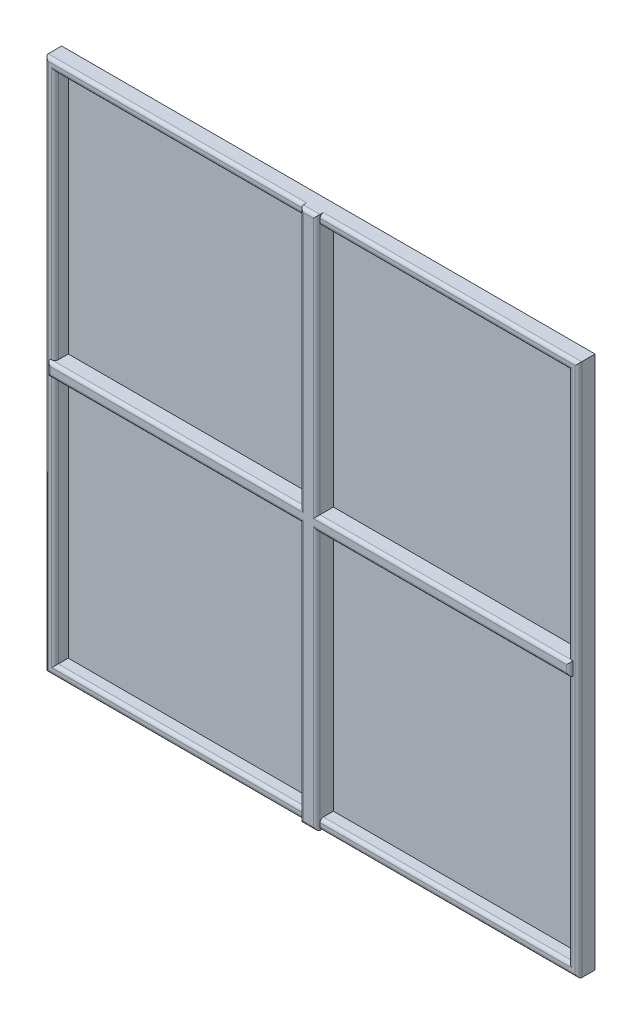
SolidWorks part; units mm, degrees
ref_plane "Front Plane" through (0, 0, 0) normal (0, 0, 1) x (1, 0, 0)
ref_plane "Top Plane" through (0, 0, 0) normal (0, 1, 0) x (1, 0, 0)
ref_plane "Right Plane" through (0, 0, 0) normal (1, 0, 0) x (0, 0, -1)
sketch "Sketch1" plane through (0, 0, 0) normal (0, 0, 1) x (1, 0, 0)
  line L0 (-1570, 30) -> (-1570, 1570)
  line L1 (0, 0) -> (-1600, 0)
  line L2 (0, 0) -> (0, 1600)
  line L3 (0, 1600) -> (-1600, 1600)
  line L4 (-1600, 0) -> (-1600, 1600)
  line L5 (-30, 1570) -> (-1570, 1570)
  line L6 (-30, 30) -> (-30, 1570)
  line L7 (-30, 30) -> (-1570, 30)
  dimension "D1" = 1600
  dimension "D2" = 1600
  dimension "D3" = 30
extrude "Boss-Extrude1" add sketch "Sketch1" along normal blind 50
fillet "Fillet1" radius 10 8 edges at (-800, 1570, 50) (-1570, 800, 50) (-800, 30, 50) (-30, 800, 50) (-800, 0, 50) (-1600, 800, 50) (-800, 1600, 50) (0, 800, 50)
sketch "Sketch2" plane through (0, 0, 0) normal (0, 0, 1) x (1, 0, 0)
  line L0 (-800, 1600) -> (-800, 0) construction
  line L1 (-1600, 1600) -> (0, 1600) construction
  line L2 (0, 0) -> (-1600, 0) construction
  line L3 (0, 800) -> (-1600, 800) construction
  line L4 (0, 1600) -> (0, 0) construction
  line L5 (-1600, 0) -> (-1600, 1600) construction
  line L6 (0, 1600) -> (-1600, 1600) construction
  line L7 (-825, 1600) -> (-775, 1600)
  line L8 (-825, 1600) -> (-825, 0)
  line L9 (-825, 0) -> (-775, 0)
  line L10 (-775, 1600) -> (-775, 0)
  line L11 (-1580, 20) -> (-1580, 1580) construction
  line L12 (-16, 820) -> (-1584, 820)
  line L13 (-16, 820) -> (-16, 780)
  line L14 (-16, 780) -> (-1584, 780)
  line L15 (-1584, 820) -> (-1584, 780)
  line L16 (-20, 1580) -> (-20, 20) construction
  line L18 (-1580, 1580) -> (-20, 1580)
  line L19 (-1580, 1580) -> (-1580, 20)
  line L20 (-1580, 20) -> (-20, 20)
  line L21 (-20, 1580) -> (-20, 20)
  dimension "D1" = 4
  dimension "D2" = 4
  dimension "D3" = 4
  dimension "D4" = 40
  dimension "D5" = 50
  dimension "D6" = 4
extrude "Boss-Extrude2" add sketch "Sketch2" along normal blind 60 contours L10 L9 L8 L7 | L12 L15 L14 L13
fillet "Fillet2" radius 10 12 edges at (-800, 0, 60) (-825, 390, 60) (-1204.5, 780, 60) (-1584, 800, 60) (-1204.5, 820, 60) (-825, 1210, 60) (-800, 1600, 60) (-775, 1210, 60) (-395.5, 820, 60) (-16, 800, 60) (-395.5, 780, 60) (-775, 390, 60)
ref_plane "Plane1" through (-825, 1580, 50) normal (1, 0, 0) x (0, 0, -1)
sketch "Sketch3" plane through (-825, 1580, 50) normal (1, 0, 0) x (0, 0, -1)
sketch "Sketch4" plane through (0, 0, 0) normal (0, 0, 1) x (1, 0, 0)
  line L1 (-1580, 1580) -> (-20, 1580)
  line L2 (-1580, 1580) -> (-1580, 20)
  line L3 (-1580, 20) -> (-20, 20)
  line L4 (-20, 1580) -> (-20, 20)
extrude "Boss-Extrude3" add sketch "Sketch4" along normal blind 10 separate body
scale "Scale1" bodies to scale 103 102 scale about origin uniform scaling yes scale factor 0.25
scale "Scale2" bodies to scale 105 104 scale about origin uniform scaling yes scale factor 0.32
